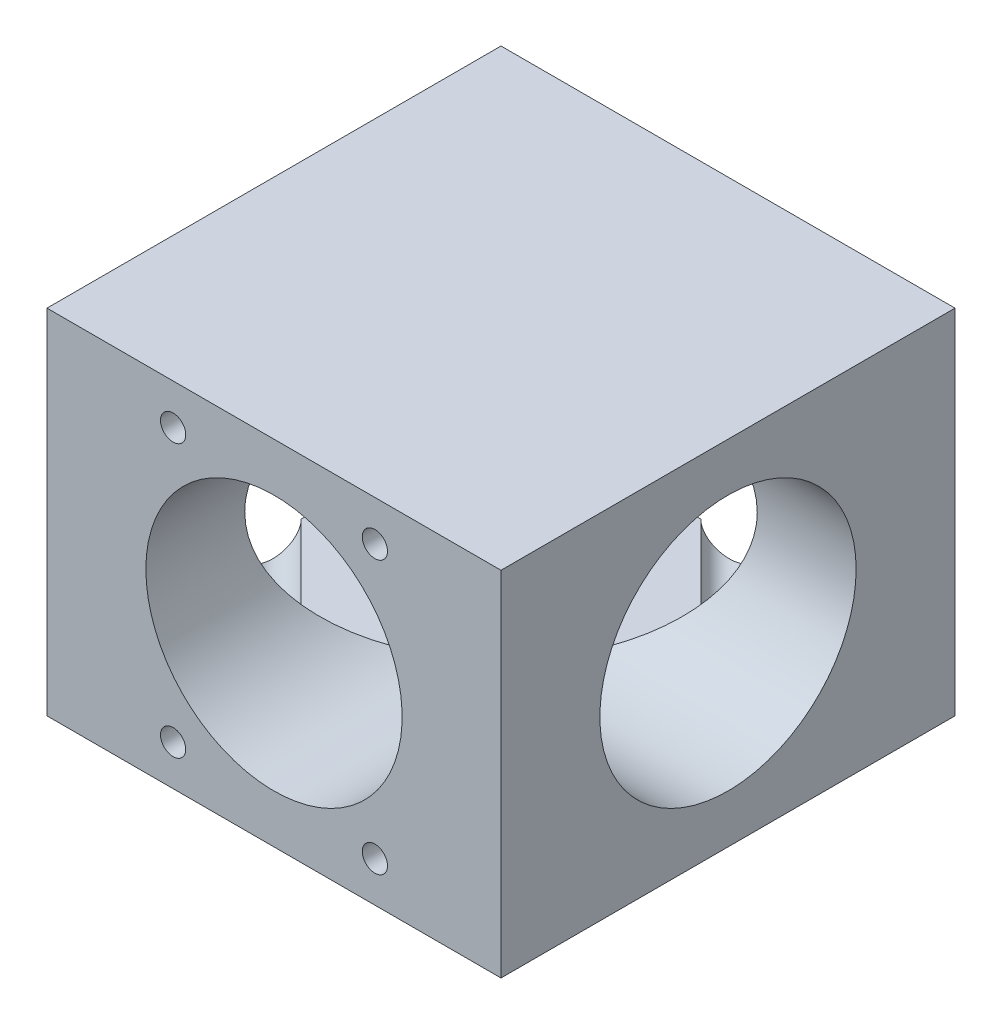
SolidWorks part; units mm, degrees
ref_plane "Front Plane" through (0, 0, 0) normal (0, 0, 1) x (1, 0, 0)
ref_plane "Top Plane" through (0, 0, 0) normal (0, 1, 0) x (1, 0, 0)
ref_plane "Right Plane" through (0, 0, 0) normal (1, 0, 0) x (0, 0, -1)
sketch "Sketch1" plane through (0, 0, 0) normal (0, 1, 0) x (1, 0, 0)
  line L1 (-22.5, -22.5) -> (22.5, -22.5)
  line L2 (-22.5, -22.5) -> (-22.5, 22.5)
  line L3 (-22.5, 22.5) -> (22.5, 22.5)
  line L4 (22.5, -22.5) -> (22.5, 22.5)
  line L5 (-22.5, -22.5) -> (22.5, 22.5) construction
  line L6 (-22.5, 22.5) -> (22.5, -22.5) construction
  point P0 (0, 0)
  dimension "D1" = 45
extrude "Boss-Extrude1" add sketch "Sketch1" along normal mid plane 35
sketch "Sketch2" plane through (22.5, 0, 0) normal (1, 0, 0) x (0, 0, -1)
  circle A0 centre (0, 0) radius 12.7
  dimension "D1" = 25.4
extrude "Cut-Extrude1" cut sketch "Sketch2" against normal up to next
sketch "Sketch3" plane through (0, 0, -22.5) normal (0, 0, -1) x (-1, 0, 0)
  circle A0 centre (0, 0) radius 12.7
  dimension "D1" = 25.4
extrude "Cut-Extrude2" cut sketch "Sketch3" against normal through all
sketch "Sketch5" plane through (0, 0, 0) normal (0, 1, 0) x (1, 0, 0)
  line L0 (-12.7279, -12.7279) -> (12.7279, 12.7279)
  line L1 (12.7279, 12.7279) -> (11.9147, 13.5411)
  line L2 (11.9147, 13.5411) -> (-13.5411, -11.9147)
  line L3 (-13.5411, -11.9147) -> (-12.7279, -12.7279)
  line L4 (22.5, -22.5) -> (22.5, 22.5) construction
  dimension "D1" = 45
  dimension "D2" = 1.15
  dimension "D3" = 36
extrude "Cut-Extrude3" cut sketch "Sketch5" against normal mid plane 26.4
sketch "Sketch7" plane through (0, 0, 0) normal (-0.7071, 0, -0.7071) x (-0.7071, 0, 0.7071)
  line L0 (-16, 13.2) -> (-16, -13.2) construction
  line L1 (-18, 13.2) -> (18, 13.2)
  line L2 (-18, 13.2) -> (-18, -13.2)
  line L3 (-18, -13.2) -> (18, -13.2)
  line L4 (18, 13.2) -> (18, -13.2)
  line L8 (-14, 13.2) -> (-14, -13.2)
  line L11 (-18, 13.2) -> (-18, -13.2)
  line L12 (16, 13.2) -> (16, -13.2) construction
  line L15 (18, 13.2) -> (18, -13.2)
  line L19 (14, 13.2) -> (14, -13.2)
  arc A4 (-14, 13.2) -> (-18, 13.2) centre (-16, 13.2) ccw
  arc A5 (-18, -13.2) -> (-14, -13.2) centre (-16, -13.2) ccw
  arc A10 (18, 13.2) -> (14, 13.2) centre (16, 13.2) ccw
  arc A11 (14, -13.2) -> (18, -13.2) centre (16, -13.2) ccw
  point P7 (-16, 0)
  point P15 (16, 0)
  point P20 (17.2994, -13.2)
  point P21 (0, 0)
  point P22 (16, 13.2)
  line M2 (-18, 13.2) -> (-18, -13.2)
  dimension "D2" = 2
extrude "Cut-Extrude4" cut sketch "Sketch7" along normal up to vertex (31.8198 mm away) contours M2 | M2 | L11 A5 L8 A4 | L2 L1 L4 L3 | L19 A11 L15 A10 region at (11.3137, 0, -11.3137) up to point (-22.5, -17.5, -22.5)
hole_wizard "M3 Tapped Hole1" positions "Sketch9" profile "Sketch10" tap size "M3" standard "DIN"
sketch "Sketch9" plane through (0, 0, 22.5) normal (0, 0, 1) x (1, 0, 0)
  line L0 (-22.5, -17.5) -> (22.5, -17.5) construction
  line L1 (-22.5, 17.5) -> (22.5, 17.5) construction
  point P0 (-10, -13.5)
  point P2 (10, -13.5)
  point P4 (10, 13.5)
  point P6 (-10, 13.5)
  point P9 (0, 0)
  point P10 (0, 0)
  point P11 (0, 0)
  dimension "D1" = 4
  dimension "D2" = 4
  dimension "D3" = 10
  dimension "D4" = 10
sketch "Sketch10" plane through (-10, -13.5, 22.5) normal (1, 0, 0) x (0, -1, 0)
  line L0 (0, 0) -> (0, 7.2511)
  line L1 (0, 7.2511) -> (1.25, 6.5)
  line L2 (1.25, 6.5) -> (1.25, 0)
  line L5 (1.25, 0) -> (0, 0)
  line L10 (0, 7.2511) -> (-1.25, 6.5) construction
  line L11 (0, -6.35) -> (0, 107.95) construction
  dimension "Tap Drill Dia." = 2.5
  dimension "Tap Drill Depth" = 6.5
  dimension "Drill Angle" = 118
cosmetic thread "Hole Thread1" parameters "D1"=5, "D2"=3
cosmetic thread "Hole Thread2" parameters "D1"=5, "D2"=3
cosmetic thread "Hole Thread3" parameters "D1"=5, "D2"=3
cosmetic thread "Hole Thread4" parameters "D1"=5, "D2"=3
hole_wizard "M3 Tapped Hole2" positions "Sketch11" profile "Sketch12" tap size "M3" standard "DIN"
sketch "Sketch11" plane through (0, 0, -22.5) normal (0, 0, -1) x (-1, 0, 0)
  circle A0 centre (-10, 13.5) radius 1.25 construction
  circle A1 centre (-10, -13.5) radius 1.25 construction
  point P0 (-10, 13.5)
  point P2 (-10, -13.5)
  point P5 (0, 0)
  point P8 (0, 0)
sketch "Sketch12" plane through (10, 13.5, -22.5) normal (1, 0, 0) x (0, 1, 0)
  line L0 (0, 0) -> (0, 6.2511)
  line L1 (0, 6.2511) -> (1.25, 5.5)
  line L2 (1.25, 5.5) -> (1.25, 0)
  line L5 (1.25, 0) -> (0, 0)
  line L10 (0, 6.2511) -> (-1.25, 5.5) construction
  line L11 (0, -6.35) -> (0, 107.95) construction
  dimension "Tap Drill Dia." = 2.5
  dimension "Tap Drill Depth" = 5.5
  dimension "Drill Angle" = 118
cosmetic thread "Hole Thread5" parameters "D1"=4, "D2"=3
cosmetic thread "Hole Thread6" parameters "D1"=4, "D2"=3
